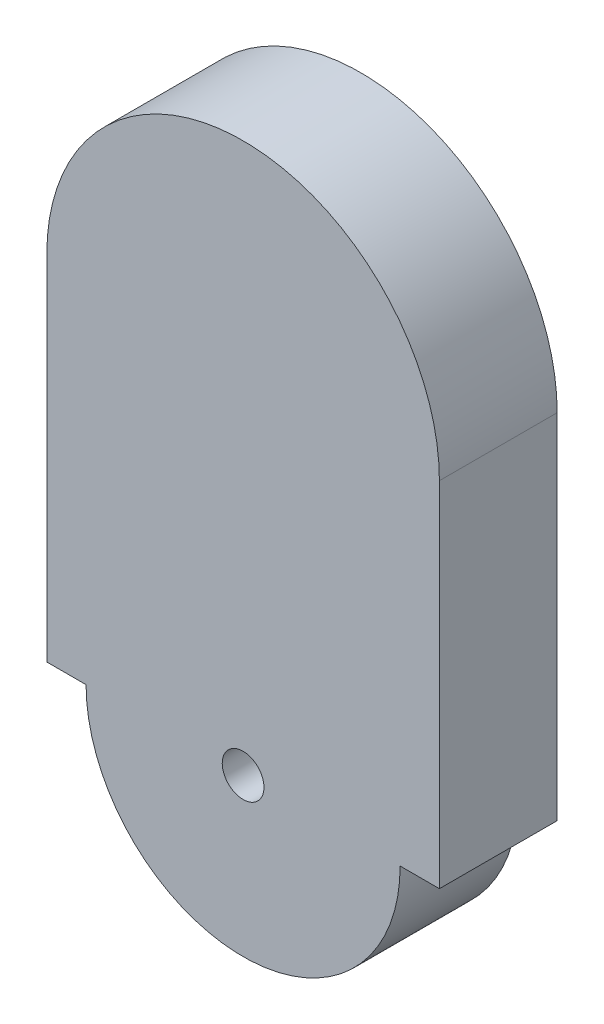
SolidWorks part; units mm, degrees
ref_plane "Front" through (0, 0, 0) normal (0, 0, 1) x (1, 0, 0)
ref_plane "Top" through (0, 0, 0) normal (0, 1, 0) x (1, 0, 0)
ref_plane "Right" through (0, 0, 0) normal (1, 0, 0) x (0, 0, -1)
sketch "Sketch2" plane through (0, 0, 0) normal (0, 0, 1) x (1, 0, 0)
  line L0 (0, 28.575) -> (0, -28.575) construction
  line L1 (0, -50) -> (0, 50) construction
  line L2 (31.75, 28.575) -> (31.75, -28.575)
  line L3 (-31.75, 28.575) -> (-31.75, -28.575)
  line L4 (-31.75, -28.575) -> (-25.4, -28.575)
  line L5 (0, -7.1144) -> (0, -28.575) construction
  line L8 (25.4, -28.575) -> (31.75, -28.575)
  line L9 (50, 0) -> (-50, 0) construction
  arc A0 (31.75, 28.575) -> (-31.75, 28.575) centre (0, 28.575) ccw
  arc A3 (-25.4, -28.575) -> (25.4, -28.575) centre (0, -28.575) ccw
  point P5 (0, 60.325)
  point P11 (0, -53.975)
  point P12 (31.75, 0)
  dimension "D2" = 31.75
  dimension "D4" = 25.4
  dimension "D1" = 63.5
  dimension "D3" = 114.3
extrude "Boss-Extrude1" add sketch "Sketch2" along normal blind 19.05
sketch "Sketch3" plane through (0, 0, 0) normal (0, 0, -1) x (-1, 0, 0)
  point P0 (0, -28.575)
hole_wizard "CBORE for 1/4 Button Head Cap Screw1" positions "Sketch4" profile "Sketch5" counterbore size "1/4" standard "ANSI Inch" end condition through all
sketch "Sketch4" plane through (0, 0, 0) normal (0, 0, -1) x (-1, 0, 0)
  point P0 (0, -28.575)
sketch "Sketch5" plane through (0, -28.575, 0) normal (1, 0, 0) x (0, 1, 0)
  line L0 (0, 0) -> (0, 19.05)
  line L1 (0, 19.05) -> (3.3782, 19.05)
  line L3 (3.3782, 19.05) -> (3.3782, 6.35)
  line L4 (3.3782, 6.35) -> (5.9538, 6.35)
  line L5 (5.9538, 6.35) -> (5.9538, 0)
  line L7 (5.9538, 0) -> (0, 0)
  line L11 (0, -6.35) -> (0, 107.95) construction
  dimension "Thru Hole Dia." = 6.7564
  dimension "Thru Hole Depth" = 19.05
  dimension "C'Bore Dia." = 11.9075
  dimension "C'Bore Depth" = 6.35
